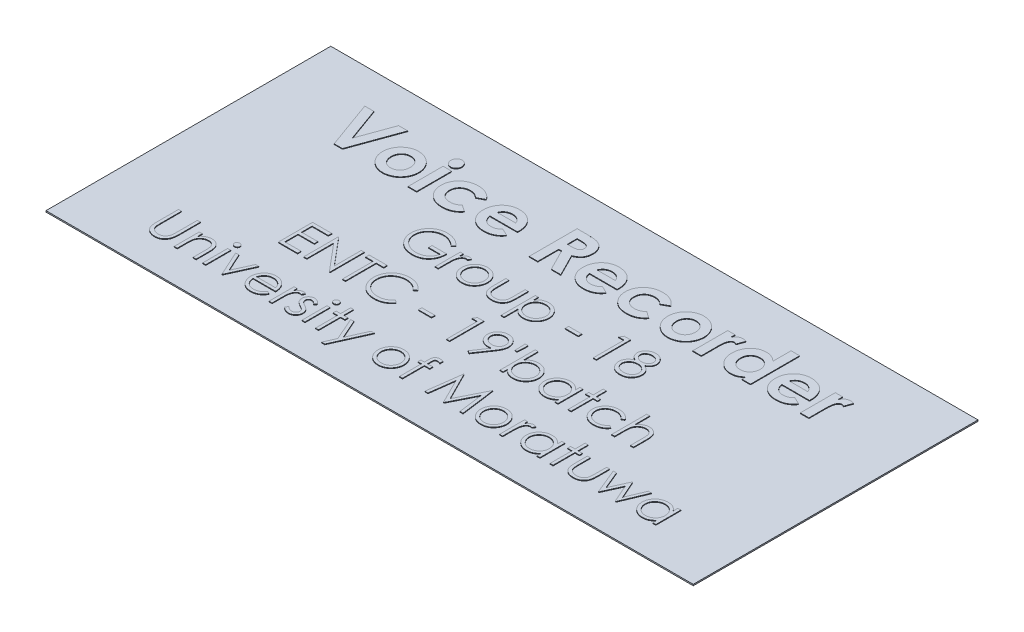
SolidWorks part; units mm, degrees
ref_plane "Front Plane" through (0, 0, 0) normal (0, 0, 1) x (1, 0, 0)
ref_plane "Top Plane" through (0, 0, 0) normal (0, 1, 0) x (1, 0, 0)
ref_plane "Right Plane" through (0, 0, 0) normal (1, 0, 0) x (0, 0, -1)
sketch "Sketch1" plane through (0, 0, 0) normal (0, 1, 0) x (1, 0, 0)
  line L1 (0, 0) -> (50, 0)
  line L2 (0, 0) -> (0, 22)
  line L3 (0, 22) -> (50, 22)
  line L4 (50, 0) -> (50, 22)
  dimension "D1" = 22
  dimension "D2" = 50
extrude "Boss-Extrude1" add sketch "Sketch1" along normal blind 0.1
sketch "Sketch2" plane through (0, 0.1, 0) normal (0, 1, 0) x (1, 0, 0)
  line L0 (1.9386, 15.5537) -> (47.6886, 15.5537) construction
  line L1 (1.9386, 11.2397) -> (47.6886, 11.2397) construction
  line L2 (1.9386, 6.8191) -> (47.6886, 6.8191) construction
  line L3 (1.9386, 2.5051) -> (47.6886, 2.5051) construction
  text T0 "<b>Voice Recorder</b>" font "Century Gothic" height in points 14
  text T1 "Group - 18" font "Century Gothic" height in points 10
  text T2 "ENTC - 19'batch" font "Century Gothic" height in points 10
  text T3 "University of Moratuwa" font "Century Gothic" height in points 10
extrude "Boss-Extrude2" add sketch "Sketch2" along normal blind 0.05
